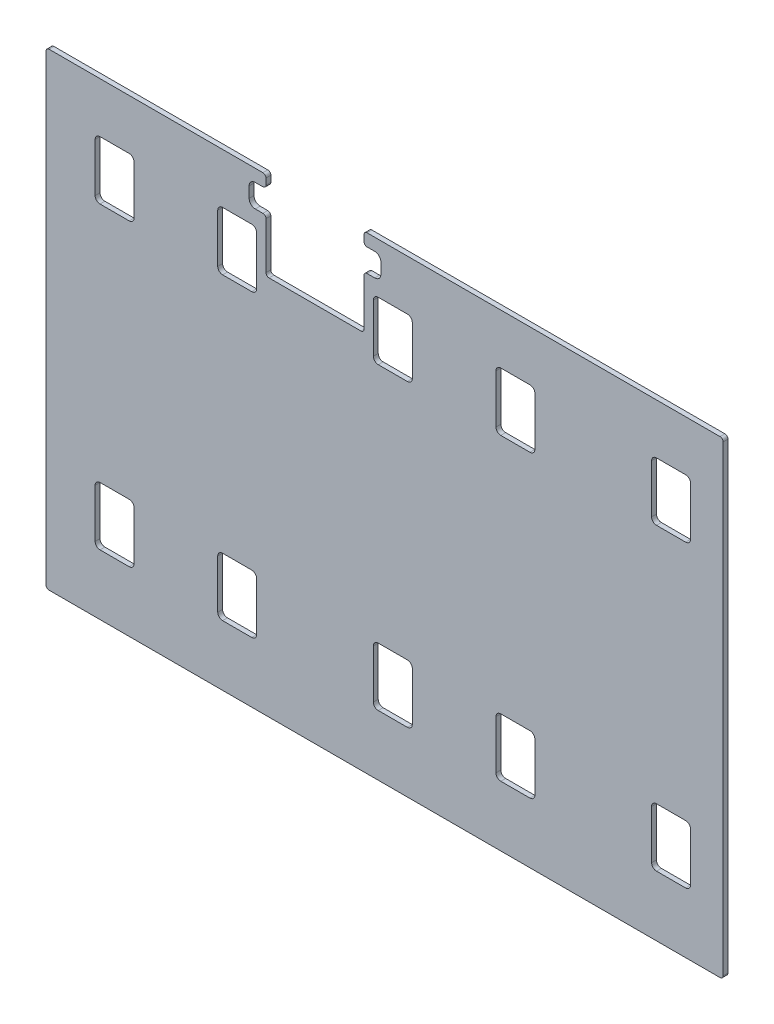
SolidWorks part; units mm, degrees
material "PP Film"
ref_plane "X-Y Datum" through (0, 0, 0) normal (0, 0, 1) x (1, 0, 0)
ref_plane "X-Z Datum" through (0, 0, 0) normal (0, 1, 0) x (1, 0, 0)
ref_plane "Y-Z Datum" through (0, 0, 0) normal (1, 0, 0) x (0, 0, -1)
sketch "Sketch1" plane through (0, 0, 0) normal (0, 0, 1) x (1, 0, 0)
  line L48 (-220.9897, 149.5877) -> (-220.9897, -156.2291)
  line L49 (-220.9897, -156.2291) -> (220.9897, -156.2291)
  line L50 (220.9897, -156.2291) -> (220.9897, 149.5877)
  line L51 (220.9897, 149.5877) -> (-220.9897, 149.5877)
extrude "Boss-Extrude1" add sketch "Sketch1" along normal blind 3.175 contours L50 L51 L48 L49 region at (0, -3.3207, 0)
sketch "Sketch2" plane through (0, 0, 3.175) normal (0, 0, 1) x (1, 0, 0)
  line L4 (-185.7466, 116.8) -> (-166.6966, 116.8)
  line L5 (-185.7466, 78.7) -> (-166.6966, 78.7)
  line L6 (-188.9216, 113.625) -> (-188.9216, 81.875)
  line L7 (-163.5216, 113.625) -> (-163.5216, 81.875)
  line L12 (-185.7466, -78.7) -> (-166.6966, -78.7)
  line L13 (-188.9216, -81.875) -> (-188.9216, -113.625)
  line L14 (-185.7466, -116.8) -> (-166.6966, -116.8)
  line L15 (-163.5216, -81.875) -> (-163.5216, -113.625)
  line L20 (-86.6814, -78.7) -> (-105.7314, -78.7)
  line L21 (-83.5064, -113.625) -> (-83.5064, -81.875)
  line L22 (-105.7314, -116.8) -> (-86.6814, -116.8)
  line L23 (-108.9064, -81.875) -> (-108.9064, -113.625)
  line L28 (-86.6814, 116.8) -> (-105.7314, 116.8)
  line L29 (-83.5064, 81.875) -> (-83.5064, 113.625)
  line L30 (-108.9064, 113.625) -> (-108.9064, 81.875)
  line L31 (-105.7314, 78.7) -> (-86.6814, 78.7)
  arc A4 (-188.9216, 81.875) -> (-185.7466, 78.7) centre (-185.7466, 81.875) ccw
  arc A5 (-185.7466, 116.8) -> (-188.9216, 113.625) centre (-185.7466, 113.625) ccw
  arc A6 (-163.5216, 113.625) -> (-166.6966, 116.8) centre (-166.6966, 113.625) ccw
  arc A7 (-166.6966, 78.7) -> (-163.5216, 81.875) centre (-166.6966, 81.875) ccw
  arc A12 (-163.5216, -81.875) -> (-166.6966, -78.7) centre (-166.6966, -81.875) ccw
  arc A13 (-185.7466, -78.7) -> (-188.9216, -81.875) centre (-185.7466, -81.875) ccw
  arc A14 (-188.9216, -113.625) -> (-185.7466, -116.8) centre (-185.7466, -113.625) ccw
  arc A15 (-166.6966, -116.8) -> (-163.5216, -113.625) centre (-166.6966, -113.625) ccw
  arc A20 (-105.7314, -78.7) -> (-108.9064, -81.875) centre (-105.7314, -81.875) ccw
  arc A21 (-83.5064, -81.875) -> (-86.6814, -78.7) centre (-86.6814, -81.875) ccw
  arc A22 (-86.6814, -116.8) -> (-83.5064, -113.625) centre (-86.6814, -113.625) ccw
  arc A23 (-108.9064, -113.625) -> (-105.7314, -116.8) centre (-105.7314, -113.625) ccw
  arc A28 (-105.7314, 116.8) -> (-108.9064, 113.625) centre (-105.7314, 113.625) ccw
  arc A29 (-83.5064, 113.625) -> (-86.6814, 116.8) centre (-86.6814, 113.625) ccw
  arc A30 (-108.9064, 81.875) -> (-105.7314, 78.7) centre (-105.7314, 81.875) ccw
  arc A31 (-86.6814, 78.7) -> (-83.5064, 81.875) centre (-86.6814, 81.875) ccw
extrude "Cut-Extrude1" cut sketch "Sketch2" against normal through all contours L14 A15 L15 A12 L12 A13 L13 A14 | L5 A7 L7 A6 L4 A5 L6 A4 region at (-176.2216, 97.75, 3.175) region at (-176.2216, -97.75, 3.175)
sketch "Sketch3" plane through (0, 0, 3.175) normal (0, 0, 1) x (1, 0, 0)
  line L4 (-166.6966, 116.8) -> (-185.7466, 116.8)
  line L5 (-163.5216, 81.875) -> (-163.5216, 113.625)
  line L6 (-185.7466, 78.7) -> (-166.6966, 78.7)
  line L7 (-188.9216, 113.625) -> (-188.9216, 81.875)
  line L8 (-166.6966, 116.8) -> (-185.7466, 116.8)
  line L9 (-163.5216, 81.875) -> (-163.5216, 113.625)
  line L10 (-185.7466, 78.7) -> (-166.6966, 78.7)
  line L11 (-188.9216, 113.625) -> (-188.9216, 81.875)
  line L12 (-188.9216, -81.875) -> (-188.9216, -113.625)
  line L13 (-185.7466, -116.8) -> (-166.6966, -116.8)
  line L14 (-163.5216, -113.625) -> (-163.5216, -81.875)
  line L15 (-166.6966, -78.7) -> (-185.7466, -78.7)
  line L16 (-188.9216, -81.875) -> (-188.9216, -113.625)
  line L17 (-185.7466, -116.8) -> (-166.6966, -116.8)
  line L18 (-163.5216, -113.625) -> (-163.5216, -81.875)
  line L19 (-166.6966, -78.7) -> (-185.7466, -78.7)
  line L20 (-86.6814, 116.8) -> (-105.7314, 116.8)
  line L21 (-108.9064, 113.625) -> (-108.9064, 81.875)
  line L22 (-105.7314, 78.7) -> (-86.6814, 78.7)
  line L23 (-83.5064, 81.875) -> (-83.5064, 113.625)
  line L24 (-86.6814, 116.8) -> (-105.7314, 116.8)
  line L25 (-108.9064, 113.625) -> (-108.9064, 81.875)
  line L26 (-105.7314, 78.7) -> (-86.6814, 78.7)
  line L27 (-83.5064, 81.875) -> (-83.5064, 113.625)
  line L28 (-105.7314, -116.8) -> (-86.6814, -116.8)
  line L29 (-83.5064, -113.625) -> (-83.5064, -81.875)
  line L30 (-86.6814, -78.7) -> (-105.7314, -78.7)
  line L31 (-108.9064, -81.875) -> (-108.9064, -113.625)
  line L32 (-105.7314, -116.8) -> (-86.6814, -116.8)
  line L33 (-83.5064, -113.625) -> (-83.5064, -81.875)
  line L34 (-86.6814, -78.7) -> (-105.7314, -78.7)
  line L35 (-108.9064, -81.875) -> (-108.9064, -113.625)
  arc A4 (-163.5216, 113.625) -> (-166.6966, 116.8) centre (-166.6966, 113.625) ccw
  arc A5 (-166.6966, 78.7) -> (-163.5216, 81.875) centre (-166.6966, 81.875) ccw
  arc A6 (-188.9216, 81.875) -> (-185.7466, 78.7) centre (-185.7466, 81.875) ccw
  arc A7 (-185.7466, 116.8) -> (-188.9216, 113.625) centre (-185.7466, 113.625) ccw
  arc A8 (-163.5216, 113.625) -> (-166.6966, 116.8) centre (-166.6966, 113.625) ccw
  arc A9 (-166.6966, 78.7) -> (-163.5216, 81.875) centre (-166.6966, 81.875) ccw
  arc A10 (-188.9216, 81.875) -> (-185.7466, 78.7) centre (-185.7466, 81.875) ccw
  arc A11 (-185.7466, 116.8) -> (-188.9216, 113.625) centre (-185.7466, 113.625) ccw
  arc A12 (-188.9216, -113.625) -> (-185.7466, -116.8) centre (-185.7466, -113.625) ccw
  arc A13 (-166.6966, -116.8) -> (-163.5216, -113.625) centre (-166.6966, -113.625) ccw
  arc A14 (-163.5216, -81.875) -> (-166.6966, -78.7) centre (-166.6966, -81.875) ccw
  arc A15 (-185.7466, -78.7) -> (-188.9216, -81.875) centre (-185.7466, -81.875) ccw
  arc A16 (-188.9216, -113.625) -> (-185.7466, -116.8) centre (-185.7466, -113.625) ccw
  arc A17 (-166.6966, -116.8) -> (-163.5216, -113.625) centre (-166.6966, -113.625) ccw
  arc A18 (-163.5216, -81.875) -> (-166.6966, -78.7) centre (-166.6966, -81.875) ccw
  arc A19 (-185.7466, -78.7) -> (-188.9216, -81.875) centre (-185.7466, -81.875) ccw
  arc A20 (-105.7314, 116.8) -> (-108.9064, 113.625) centre (-105.7314, 113.625) ccw
  arc A21 (-108.9064, 81.875) -> (-105.7314, 78.7) centre (-105.7314, 81.875) ccw
  arc A22 (-86.6814, 78.7) -> (-83.5064, 81.875) centre (-86.6814, 81.875) ccw
  arc A23 (-83.5064, 113.625) -> (-86.6814, 116.8) centre (-86.6814, 113.625) ccw
  arc A24 (-105.7314, 116.8) -> (-108.9064, 113.625) centre (-105.7314, 113.625) ccw
  arc A25 (-108.9064, 81.875) -> (-105.7314, 78.7) centre (-105.7314, 81.875) ccw
  arc A26 (-86.6814, 78.7) -> (-83.5064, 81.875) centre (-86.6814, 81.875) ccw
  arc A27 (-83.5064, 113.625) -> (-86.6814, 116.8) centre (-86.6814, 113.625) ccw
  arc A28 (-86.6814, -116.8) -> (-83.5064, -113.625) centre (-86.6814, -113.625) ccw
  arc A29 (-83.5064, -81.875) -> (-86.6814, -78.7) centre (-86.6814, -81.875) ccw
  arc A30 (-105.7314, -78.7) -> (-108.9064, -81.875) centre (-105.7314, -81.875) ccw
  arc A31 (-108.9064, -113.625) -> (-105.7314, -116.8) centre (-105.7314, -113.625) ccw
  arc A32 (-86.6814, -116.8) -> (-83.5064, -113.625) centre (-86.6814, -113.625) ccw
  arc A33 (-83.5064, -81.875) -> (-86.6814, -78.7) centre (-86.6814, -81.875) ccw
  arc A34 (-105.7314, -78.7) -> (-108.9064, -81.875) centre (-105.7314, -81.875) ccw
  arc A35 (-108.9064, -113.625) -> (-105.7314, -116.8) centre (-105.7314, -113.625) ccw
  dimension "D1" = 0
  dimension "D2" = 0
  dimension "D3" = 0
  dimension "D4" = 0
extrude "Cut-Extrude2" cut sketch "Sketch3" against normal through all contours L35 A35 L32 A32 L33 A33 L34 A34 | L27 A27 L24 A24 L25 A25 L26 A26 region at (-96.2064, 97.75, 3.175) region at (-96.2064, -97.75, 3.175)
pattern_linear "LPattern1" count 3 spacing 181.614 along (1, 0, 0) of "Cut-Extrude1"
pattern_linear "LPattern2" count 2 spacing 181.614 along (1, 0, 0) of "Cut-Extrude2"
sketch "Sketch6" plane through (0, 0, 3.175) normal (0, 0, 1) x (1, 0, 0)
  line L0 (-72.407, 92.0877) -> (-18.407, 92.0877)
  line L1 (-77.407, 149.5877) -> (-77.407, 92.0877)
  line L2 (-77.407, 92.0877) -> (-72.407, 92.0877)
  line L3 (-18.407, 92.0877) -> (-13.407, 92.0877)
  line L11 (-77.407, 141.5877) -> (-84.407, 141.5877)
  line L12 (-6.407, 141.5877) -> (-13.407, 141.5877)
  line L13 (-77.407, 149.0877) -> (-77.407, 92.0877) construction
  line L14 (-86.407, 137.5877) -> (-86.407, 130.5877) construction
  line L15 (-84.407, 128.5877) -> (-77.407, 128.5877) construction
  line L16 (-75.407, 126.5877) -> (-75.407, 141.5877) construction
  line L17 (-77.407, 139.5877) -> (-84.407, 139.5877) construction
  line L24 (-13.407, 92.0877) -> (-13.407, 149.0877) construction
  line L28 (-13.407, 128.5877) -> (-6.407, 128.5877) construction
  line L29 (-4.407, 130.5877) -> (-4.407, 137.5877) construction
  line L30 (-6.407, 139.5877) -> (-13.407, 139.5877) construction
  line L34 (-15.407, 141.5877) -> (-15.407, 126.5877) construction
  line L36 (-72.407, 94.0877) -> (-18.407, 94.0877) construction
  line L37 (-18.407, 94.0877) -> (-18.407, 149.0877) construction
  line L38 (-18.407, 149.0877) -> (-72.407, 149.0877) construction
  line L39 (-72.407, 149.0877) -> (-72.407, 94.0877) construction
  line L44 (-75.407, 94.0877) -> (-72.407, 94.0877) construction
  line L45 (-72.407, 94.0877) -> (-72.407, 149.0877) construction
  line L46 (-72.407, 149.0877) -> (-75.407, 149.0877) construction
  line L47 (-75.407, 149.0877) -> (-75.407, 94.0877) construction
  line L52 (-15.407, 149.0877) -> (-18.407, 149.0877) construction
  line L53 (-18.407, 149.0877) -> (-18.407, 94.0877) construction
  line L54 (-18.407, 94.0877) -> (-15.407, 94.0877) construction
  line L55 (-15.407, 94.0877) -> (-15.407, 149.0877) construction
  line L56 (-13.407, 92.0877) -> (-13.407, 149.5877)
  line L57 (-13.407, 126.5877) -> (-6.407, 126.5877)
  line L58 (-2.407, 130.5877) -> (-2.407, 149.5877)
  line L59 (-88.407, 149.5877) -> (-88.407, 130.5877)
  line L60 (-84.407, 126.5877) -> (-77.407, 126.5877)
  line L61 (-88.407, 137.5877) -> (-88.407, 130.5877) construction
  line L63 (-2.407, 130.5877) -> (-2.407, 137.5877) construction
  line L64 (220.9897, 149.5877) -> (-220.9897, 149.5877)
  line L65 (-88.407, 149.5877) -> (-2.407, 149.5877)
  arc A0 (-13.407, 126.5877) -> (-13.407, 126.5877) centre (-13.407, 126.5877) cw
  arc A1 (-6.407, 126.5877) -> (-2.407, 130.5877) centre (-6.407, 130.5877) ccw
  arc A2 (-88.407, 130.5877) -> (-84.407, 126.5877) centre (-84.407, 130.5877) ccw
  arc A5 (-84.407, 139.5877) -> (-86.407, 137.5877) centre (-84.407, 137.5877) ccw
  arc A7 (-86.407, 130.5877) -> (-84.407, 128.5877) centre (-84.407, 130.5877) ccw
  arc A13 (-4.407, 137.5877) -> (-6.407, 139.5877) centre (-6.407, 137.5877) ccw
  arc A15 (-15.407, 141.5877) -> (-13.407, 139.5877) centre (-13.407, 141.5877) ccw
  arc A31 (-84.407, 141.5877) -> (-88.407, 137.5877) centre (-84.407, 137.5877) ccw
  arc A32 (-2.407, 137.5877) -> (-6.407, 141.5877) centre (-6.407, 137.5877) ccw
  arc A35 (-86.407, 130.5877) -> (-84.407, 128.5877) centre (-84.407, 130.5877) ccw construction
  arc A37 (-75.407, 126.5877) -> (-77.407, 128.5877) centre (-77.407, 126.5877) ccw
  arc A39 (-77.407, 139.5877) -> (-75.407, 141.5877) centre (-77.407, 141.5877) ccw
  arc A40 (-6.407, 128.5877) -> (-4.407, 130.5877) centre (-6.407, 130.5877) ccw construction
  arc A41 (-13.407, 128.5877) -> (-15.407, 126.5877) centre (-13.407, 126.5877) ccw construction
  arc A43 (-13.407, 128.5877) -> (-15.407, 126.5877) centre (-13.407, 126.5877) ccw
  arc A45 (-6.407, 128.5877) -> (-4.407, 130.5877) centre (-6.407, 130.5877) ccw
  dimension "D6" = 2
  dimension "D7" = 2
  dimension "D8" = 2
extrude "Cut-Extrude3" cut sketch "Sketch6" against normal through all contours L59 A2 L60 L1 L2 L0 L3 L56 L57 A1 L58 L64 | L11 A31 L59 A2 L60 L1 | L58 A32 L12 L56 L57 A1 region at (-45.407, 120.8377, 3.175) region at (-82.707, 134.0877, 3.175) region at (-8.107, 134.0877, 3.175)
fillet "Fillet1" radius 2 12 edges at (-13.407, 126.5877, 1.5875) (-13.407, 92.0877, 1.5875) (-77.407, 92.0877, 1.5875) (-77.407, 126.5877, 1.5875) (-13.407, 141.5877, 1.5875) (-77.407, 141.5877, 1.5875) (-13.407, 149.5877, 1.5875) (-77.407, 149.5877, 1.5875) (220.9897, 149.5877, 1.5875) (-220.9897, 149.5877, 1.5875) (-220.9897, -156.2291, 1.5875) (220.9897, -156.2291, 1.5875)
